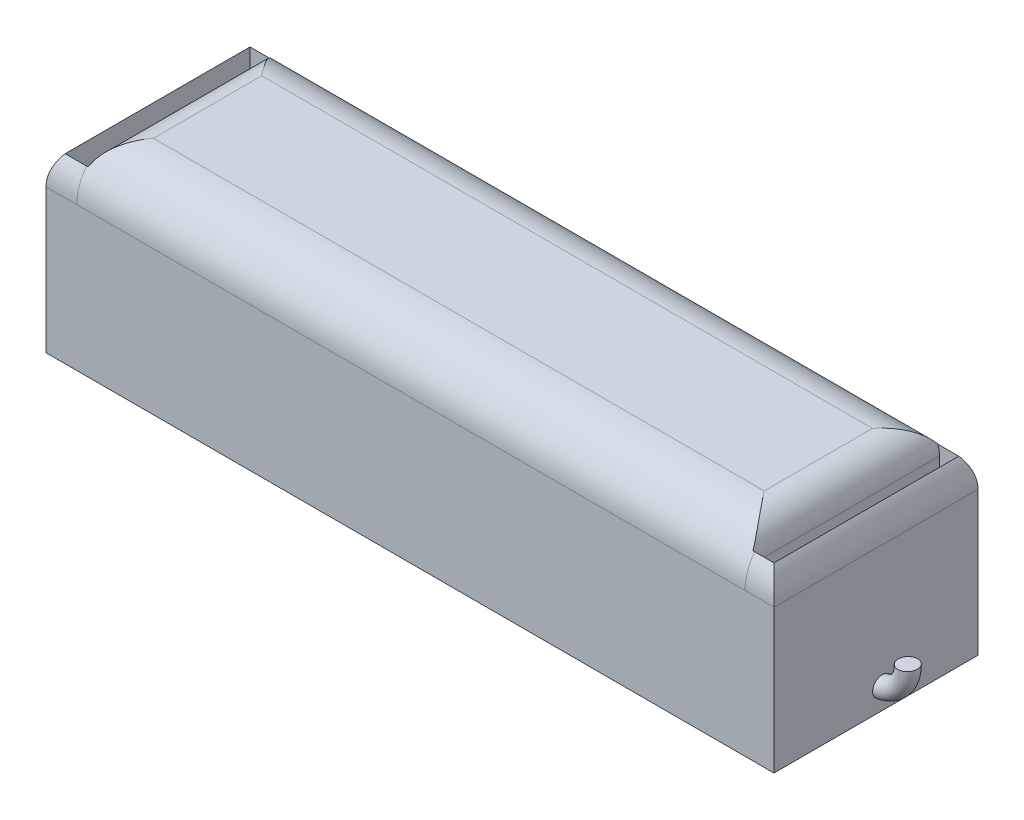
SolidWorks part; units mm, degrees
ref_plane "前视基准面" through (0, 0, 0) normal (0, 0, 1) x (1, 0, 0)
ref_plane "上视基准面" through (0, 0, 0) normal (0, 1, 0) x (1, 0, 0)
ref_plane "右视基准面" through (0, 0, 0) normal (1, 0, 0) x (0, 0, -1)
sketch "草图1" plane through (0, 0, 0) normal (0, 1, 0) x (1, 0, 0)
  line L1 (-38, 10.65) -> (38, 10.65)
  line L2 (-38, 10.65) -> (-38, -10.65)
  line L3 (-38, -10.65) -> (38, -10.65)
  line L4 (38, 10.65) -> (38, -10.65)
  line L5 (-38, 10.65) -> (38, -10.65) construction
  line L6 (-38, -10.65) -> (38, 10.65) construction
  point P0 (0, 0)
  dimension "D1" = 76
  dimension "D2" = 21.3
extrude "凸台-拉伸1" add sketch "草图1" along normal blind 20
ref_plane "基准面1" through (0, 0, -0.65) normal (0, 0, -1) x (-1, 0, 0)
shell "抽壳1" thickness 1
fillet "圆角1" radius 5 4 edges at (0, 20, 10.65) (-38, 20, 0) (0, 20, -10.65) (38, 20, 0)
sketch "草图28" plane through (0, 0, -0.65) normal (0, 0, -1) x (-1, 0, 0)
  line L1 (0, 0) -> (0, 15) construction
  line L2 (38, 15) -> (-38, 15) construction
  arc A0 (-36.2336, 2.3826) -> (-40.6667, 5.5375) centre (-37.413, 5.4175) cw
sweep "扫描6" add path "草图28" circular profile diameter 2 parameters "D3"=2
mirror "镜向1" about plane through (0, 0, 0) normal (1, 0, 0) of "扫描6"
sketch "草图31" plane through (0, 0, 0) normal (0, -1, 0) x (1, 0, 0)
  line L0 (-38, 10.65) -> (38, 10.65) construction
  line L1 (-34.7829, 10.65) -> (34.9807, 10.65)
  line L2 (-34.7829, 10.65) -> (-34.7829, -10.65)
  line L3 (-34.7829, -10.65) -> (34.9807, -10.65)
  line L4 (34.9807, 10.65) -> (34.9807, -10.65)
extrude "凸台-拉伸2" add sketch "草图31" against normal blind 20
fillet "圆角2" radius 5 2 edges at (0.0989, 20, 10.65) (0.0989, 20, -10.65)
fillet "圆角3" radius 3 2 edges at (-34.7829, 20, 0) (34.9807, 20, 0)
